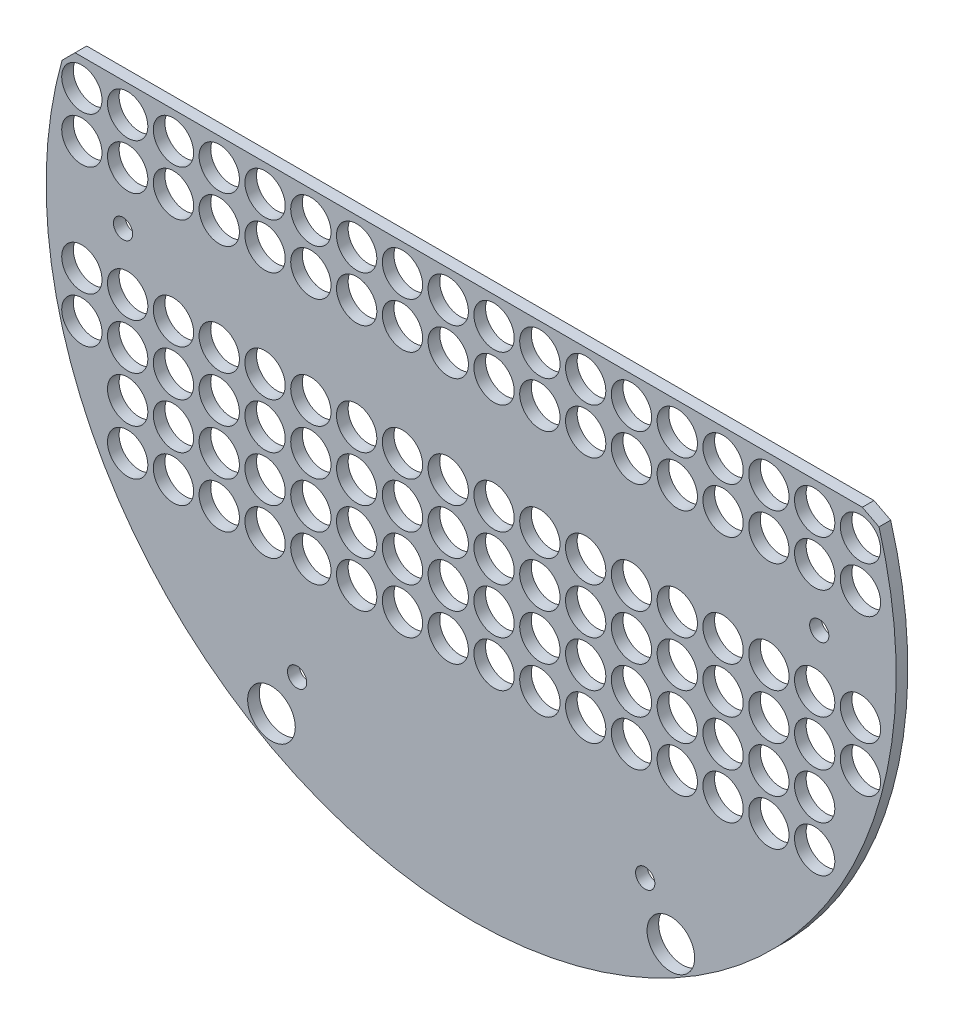
SolidWorks part; units mm, degrees
ref_plane "Front Plane" through (0, 0, 0) normal (0, 0, 1) x (1, 0, 0)
ref_plane "Top Plane" through (0, 0, 0) normal (0, 1, 0) x (1, 0, 0)
ref_plane "Right Plane" through (0, 0, 0) normal (1, 0, 0) x (0, 0, -1)
sketch "Sketch1" plane through (0, 0, 0) normal (0, 0, 1) x (1, 0, 0)
  line L0 (-221.1877, 70) -> (221.1877, 70)
  arc A0 (-221.1877, 70) -> (221.1877, 70) centre (0, 0) ccw
  dimension "D1" = 464
  dimension "D2" = 70
extrude "Boss-Extrude1" add sketch "Sketch1" along normal blind 6.35
chamfer "Chamfer1" distance 5 angle 45 2 edges at (-221.1877, 70, 3.175) (221.1877, 70, 3.175) first distance on face at (0, 70, 3.175) first distance on face at (0, -81, 3.175)
sketch "Sketch2" plane through (0, 0, 6.35) normal (0, 0, 1) x (1, 0, 0)
  circle A1 centre (-190, 0) radius 5.25
  circle A4 centre (190, 0) radius 5.25
  circle A5 centre (95, -164.5448) radius 5.25
  circle A6 centre (-95, -164.5448) radius 5.25
  arc A7 (-189.9275, 5.2495) -> (189.9275, 5.2495) centre (0, 0) ccw construction
  arc A8 (-99.5099, 161.8573) -> (-90.4175, 167.1068) centre (-95, 164.5448) ccw [skipped]
  arc A9 (99.5099, 161.8573) -> (90.4175, 167.1068) centre (95, 164.5448) ccw [skipped]
  point P18 (0, 0)
  dimension "D1" = 190
  dimension "D2" = 10.5
  dimension "D4" = 190
  dimension "D5" = 164.5448
  dimension "D6" = 95
  dimension "D3" = 6
extrude "Cut-Extrude1" cut sketch "Sketch2" against normal through all
sketch "Sketch3" plane through (0, 0, 6.35) normal (0, 0, 1) x (1, 0, 0)
  line L0 (0, 140.2547) -> (0, -298.7075) construction
  line L1 (-353.8302, 0) -> (406.1509, 0) construction
  circle A0 centre (12.5, -30) radius 11
  circle A1 centre (12.5, -55) radius 11
  circle A2 centre (12.5, -80) radius 11
  circle A3 centre (12.5, -105) radius 11
  circle A4 centre (37.5, -30) radius 11
  circle A5 centre (37.5, -55) radius 11
  circle A6 centre (62.5, -30) radius 11
  circle A7 centre (62.5, -55) radius 11
  circle A8 centre (87.5, -30) radius 11
  circle A9 centre (87.5, -55) radius 11
  circle A10 centre (112.5, -30) radius 11
  circle A11 centre (112.5, -55) radius 11
  circle A12 centre (137.5, -30) radius 11
  circle A13 centre (137.5, -55) radius 11
  circle A14 centre (162.5, -30) radius 11
  circle A15 centre (162.5, -55) radius 11
  circle A16 centre (187.5, -30) radius 11
  circle A17 centre (187.5, -55) radius 11
  circle A18 centre (212.5, -30) radius 11
  circle A19 centre (212.5, -55) radius 11
  circle A20 centre (37.5, -80) radius 11
  circle A21 centre (37.5, -105) radius 11
  circle A22 centre (62.5, -80) radius 11
  circle A23 centre (62.5, -105) radius 11
  circle A24 centre (87.5, -80) radius 11
  circle A25 centre (87.5, -105) radius 11
  circle A26 centre (112.5, -80) radius 11
  circle A27 centre (112.5, -105) radius 11
  circle A28 centre (137.5, -80) radius 11
  circle A29 centre (137.5, -105) radius 11
  circle A30 centre (162.5, -80) radius 11
  circle A31 centre (162.5, -105) radius 11
  circle A32 centre (187.5, -80) radius 11
  circle A33 centre (187.5, -105) radius 11
  circle A34 centre (12.5, 30) radius 11
  circle A35 centre (12.5, 55) radius 11
  circle A36 centre (37.5, 55) radius 11
  circle A37 centre (37.5, 30) radius 11
  circle A38 centre (62.5, 55) radius 11
  circle A39 centre (62.5, 30) radius 11
  circle A40 centre (87.5, 55) radius 11
  circle A41 centre (87.5, 30) radius 11
  circle A42 centre (112.5, 55) radius 11
  circle A43 centre (112.5, 30) radius 11
  circle A44 centre (137.5, 55) radius 11
  circle A45 centre (137.5, 30) radius 11
  circle A46 centre (162.5, 55) radius 11
  circle A47 centre (162.5, 30) radius 11
  circle A48 centre (187.5, 55) radius 11
  circle A49 centre (187.5, 30) radius 11
  circle A50 centre (212.5, 55) radius 11
  circle A51 centre (212.5, 30) radius 11
  dimension "D1" = 22
  dimension "D2" = 22
  dimension "D3" = 22
  dimension "D4" = 22
  dimension "D14" = 22
  dimension "D15" = 22
  dimension "D5" = 12.5
  dimension "D6" = 30
  dimension "D7" = 55
  dimension "D8" = 80
  dimension "D9" = 105
  dimension "D12" = 37.5
  dimension "D13" = 37.5
  dimension "D16" = 30
  dimension "D17" = 55
  dimension "D19" = 37.5
  dimension "D10" = 9
  dimension "D11" = 8
  dimension "D18" = 9
extrude "Cut-Extrude2" cut sketch "Sketch3" against normal through all
mirror "Mirror2" about plane through (0, 0, 0) normal (1, 0, 0) of "Cut-Extrude2"
sketch "Sketch4" plane through (0, 0, 6.35) normal (0, 0, 1) x (1, 0, 0)
  line L0 (0, 0) -> (-147.2629, -255.0668) construction
  line L1 (0, 0) -> (147.2629, -255.0668) construction
  line L2 (0, 0) -> (0, -304.2802) construction
  circle A0 centre (0, 0) radius 218 construction
  circle A1 centre (-109, -188.7935) radius 13
  circle A2 centre (109, -188.7935) radius 13
  dimension "D1" = 436
  dimension "D2" = 26
  dimension "D3" = 26
  dimension "D4" = 60
extrude "Cut-Extrude3" cut sketch "Sketch4" against normal through all
